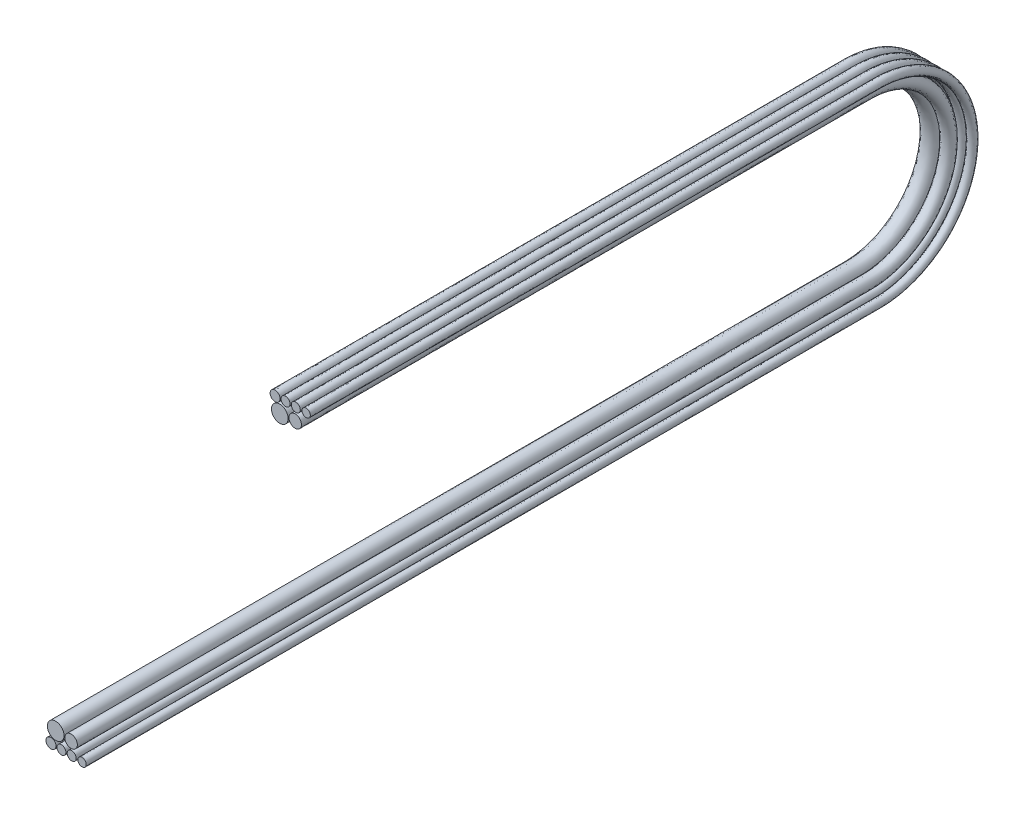
SolidWorks part; units mm, degrees
ref_plane "Front Plane" through (0, 0, 0) normal (0, 0, 1) x (1, 0, 0)
ref_plane "Top Plane" through (0, 0, 0) normal (0, 1, 0) x (1, 0, 0)
ref_plane "Right Plane" through (0, 0, 0) normal (1, 0, 0) x (0, 0, -1)
sketch "Sketch1" plane through (0, 0, 0) normal (0, 0, 1) x (1, 0, 0)
  line L1 (18.5, 18) -> (-18.5, 18) construction
  line L2 (18.5, 18) -> (18.5, 0) construction
  line L3 (18.5, 0) -> (-18.5, 0) construction
  line L4 (-18.5, 18) -> (-18.5, 0) construction
  circle A0 centre (-16.1, 2.4) radius 2.4
  circle A2 centre (-11.0983, 2.15) radius 2.15
  circle A5 centre (-6.1615, 2.15) radius 2.15
  circle A6 centre (-1.1864, 2) radius 2
  circle A7 centre (-13.8535, 8.6823) radius 4
  circle A8 centre (-6.4473, 8.0498) radius 3
  dimension "D3" = 4.8
  dimension "D4" = 4.3
  dimension "D6" = 4
  dimension "D7" = 8
  dimension "D8" = 6
  dimension "D1" = 37
  dimension "D2" = 18
sketch "Sketch2" plane through (0, 0, 0) normal (1, 0, 0) x (0, 0, -1)
  spline S1 degree 3 poles (-999.9965, 9.7) (-539.4624, 9.7) (-78.8563, 9.7) (381.8218, 9.7) (382.0378, 9.7023) (382.1817, 9.7043) (382.2537, 9.7055) (455.7262, 10.9584) (455.7262, 84.4416) (382.2537, 85.6945) (382.1817, 85.6957) (382.0378, 85.6977) (381.8218, 85.7) (-42.9915, 85.7) (-467.7328, 85.7) (-892.4021, 85.7) knots -1.36443 -1.36443 -1.36443 -1.36443 0.520676 0.520971 0.521266 0.52156 0.52156 0.52156 0.625242 0.625242 0.625242 0.625537 0.625832 0.626126 2.364427 2.364427 2.364427 2.364427 weights 1 1 1 1 1 1 1 0.3447 0.3447 1 1 1 1 1 1 1 only from (0, 9.7) to (107.5921, 85.7) construction
  spline S2 degree 3 poles (0, 9.7) (127.2019, 9.7) (254.4759, 9.7) (381.8218, 9.7) (382.0378, 9.7023) (382.1817, 9.7043) (382.2537, 9.7055) (455.7262, 10.9584) (455.7262, 84.4416) (382.2537, 85.6945) (382.1817, 85.6957) (382.0378, 85.6977) (381.8218, 85.7) (290.3399, 85.7) (198.93, 85.7) (107.5921, 85.7) knots 0 0 0 0 0.520676 0.520971 0.521266 0.52156 0.52156 0.52156 0.625242 0.625242 0.625242 0.625537 0.625832 0.626126 1 1 1 1 weights 1 1 1 1 1 1 1 0.3447 0.3447 1 1 1 1 1 1 1
sweep "Sweep1" add profiles "Sketch1" path "Sketch2"
